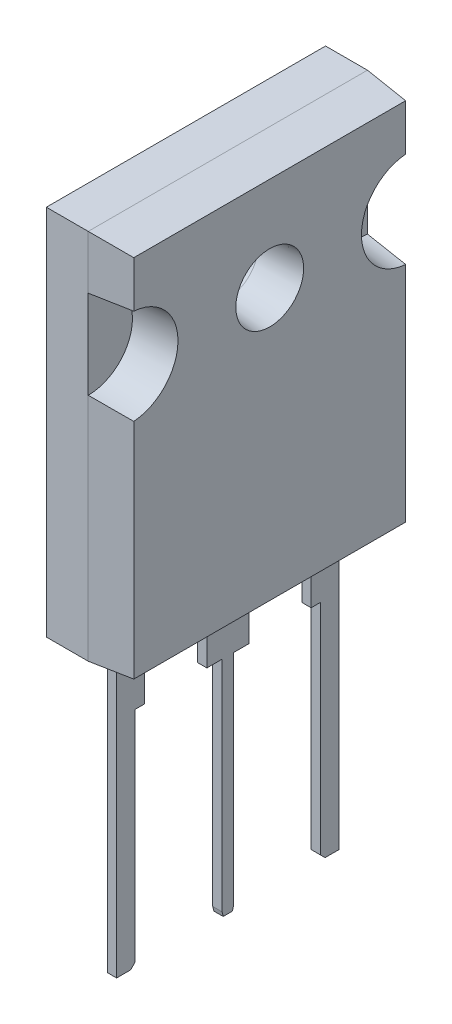
SolidWorks part; units mm, degrees
ref_plane "Front Plane" through (0, 0, 0) normal (0, 0, 1) x (1, 0, 0)
ref_plane "Top Plane" through (0, 0, 0) normal (0, 1, 0) x (1, 0, 0)
ref_plane "Right Plane" through (0, 0, 0) normal (1, 0, 0) x (0, 0, -1)
sketch "Sketch2" plane through (0, 0, 0) normal (1, 0, 0) x (0, 0, -1)
  line L0 (7.62, -2.413) -> (7.62, -14.986)
  line L1 (-7.62, 5.334) -> (7.62, 5.334)
  line L2 (-7.62, 5.334) -> (-7.62, 2.413)
  line L3 (-7.62, -14.986) -> (7.62, -14.986)
  line L4 (7.62, 5.334) -> (7.62, 2.413)
  line L5 (0, -17.9025) -> (0, 11.7071) construction
  line L6 (-7.62, -2.413) -> (-7.62, -14.986)
  arc A1 (7.62, 2.413) -> (7.62, -2.413) centre (7.62, 0) ccw
  arc A2 (-7.62, 2.413) -> (-7.62, -2.413) centre (-7.62, 0) cw
  dimension "D1" = 5.334
  dimension "D6" = 4.826
  dimension "D2" = 7.62
  dimension "D3" = 2.921
  dimension "D5" = 20.32
extrude "Extrude1" add sketch "Sketch2" along normal blind 2.286 draft 5 contours L4 L1 L2 L3 | L5 L3 L0 A1 L4 L1 region at (0, -5.129, 0)
sketch "Sketch6" plane through (0, 0, 0) normal (-1, 0, 0) x (0, 0, 1)
  line L1 (-7.62, 5.334) -> (7.62, 5.334)
  line L2 (-7.62, 5.334) -> (-7.62, -14.986)
  line L3 (-7.62, -14.986) -> (7.62, -14.986)
  line L4 (7.62, 5.334) -> (7.62, -14.986)
extrude "Extrude2" add sketch "Sketch6" along normal blind 2.286
sketch "Sketch7" plane through (2.286, 0, 0) normal (1, 0, 0) x (0, 0, -1)
  circle A0 centre (0, 0) radius 1.651
  dimension "D1" = 3.302
extrude "Cut-Extrude3" cut sketch "Sketch7" against normal through all normal cut yes
sketch "Sketch9" plane through (0, 0, 0) normal (1, 0, 0) x (0, 0, -1)
  circle A0 centre (0, 0) radius 1.651
  dimension "D1" = 3.302
extrude "Cut-Extrude6" cut sketch "Sketch9" along normal blind 2.286 draft 5 normal cut yes draft outward yes
sketch "Sketch10" plane through (0, 0, 0) normal (0, 0, 1) x (1, 0, 0)
  line L0 (0, -14.986) -> (0, -30.734)
  line L1 (2.286, -14.786) -> (0, -14.986) construction
  line L2 (-2.286, -14.986) -> (-2.286, 5.334) construction
  dimension "D1" = 15.748
  dimension "D2" = 2.286
sheet metal parameters "Sheet-Metal1" thickness 0.508 parameters "D1"=0.762
base flange "Base-Flange1" sketch "Sketch10" end condition mid plane depth 2.286 reverse direction no thickness 0.508 reverse thickness direction no bend radius 0.762
sketch "Sketch13" plane through (0, 0, 0) normal (1, 0, 0) x (0, 0, -1)
  line L0 (0, 6.4433) -> (0, -32.38) construction
  line L1 (-1.143, -14.986) -> (1.143, -14.986) construction
  line L2 (-1.143, -30.734) -> (-0.254, -30.734)
  line L3 (-1.143, -30.734) -> (-1.143, -18.542)
  line L4 (-1.143, -18.542) -> (-0.3175, -18.542)
  line L5 (-0.3175, -30.48) -> (-0.3175, -18.542)
  line L6 (-0.254, -30.734) -> (-0.3175, -30.48)
  line L7 (0.254, -30.734) -> (0.3175, -30.48)
  line L8 (0.3175, -30.48) -> (0.3175, -18.542)
  line L9 (1.143, -18.542) -> (0.3175, -18.542)
  line L10 (1.143, -30.734) -> (1.143, -18.542)
  line L11 (1.143, -30.734) -> (0.254, -30.734)
  dimension "D1" = 0.635
  dimension "D2" = 3.556
  dimension "D3" = 0.254
  dimension "D4" = 0.254
extrude "Cut-Extrude8" cut sketch "Sketch13" against normal through all normal cut yes
sketch "Sketch15" plane through (0, 0, 0) normal (1, 0, 0) x (0, 0, -1)
  line L0 (-7.62, -14.986) -> (7.62, -14.986) construction
  line L1 (-6.0706, -14.986) -> (-4.5466, -14.986)
  line L2 (-6.0706, -14.986) -> (-6.0706, -30.734)
  line L3 (-6.0706, -30.734) -> (-5.3086, -30.734)
  line L4 (-4.5466, -14.986) -> (-4.5466, -18.542)
  line L6 (-5.5626, -32.5888) -> (-5.5626, -13.5219) construction
  line L7 (-5.3086, -30.734) -> (-5.0546, -30.48)
  line L8 (0, 9.0004) -> (0, -42.1241) construction
  line L9 (5.5626, -32.5888) -> (5.5626, -13.5219) construction
  line L10 (-4.5466, -18.542) -> (-5.0546, -18.542)
  line L11 (-5.0546, -30.48) -> (-5.0546, -18.542)
  line L12 (5.0546, -30.48) -> (5.0546, -18.542)
  line L13 (4.5466, -18.542) -> (5.0546, -18.542)
  line L14 (5.3086, -30.734) -> (5.0546, -30.48)
  line L15 (4.5466, -14.986) -> (4.5466, -18.542)
  line L16 (6.0706, -30.734) -> (5.3086, -30.734)
  line L17 (6.0706, -14.986) -> (6.0706, -30.734)
  line L18 (6.0706, -14.986) -> (4.5466, -14.986)
  dimension "D1" = 15.748
  dimension "D2" = 5.5626
  dimension "D3" = 0.508
  dimension "D4" = 0.508
  dimension "D5" = 1.016
  dimension "D6" = 3.556
  dimension "D7" = 0.254
  dimension "D8" = 0.254
extrude "Extrude3" add sketch "Sketch15" against normal blind 0.508
flat pattern "Flat-Pattern1" [suppressed]
sketch "Bend-Lines1" plane through (0, 0, 0) normal (0, 1, 0) x (-1, 0, 0)
